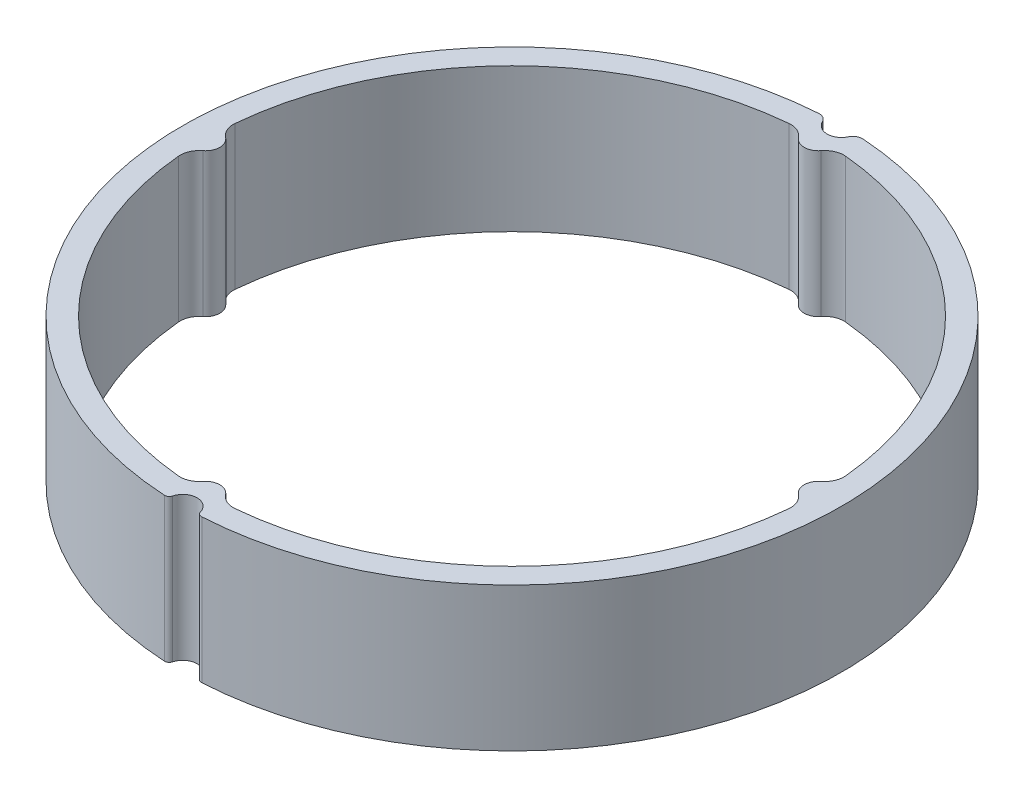
SolidWorks part; units mm, degrees
ref_plane "Front Plane" through (0, 0, 0) normal (0, 0, 1) x (1, 0, 0)
ref_plane "Top Plane" through (0, 0, 0) normal (0, 1, 0) x (1, 0, 0)
ref_plane "Right Plane" through (0, 0, 0) normal (1, 0, 0) x (0, 0, -1)
sketch "Sketch1" plane through (0, 0, 0) normal (0, 1, 0) x (1, 0, 0)
  line L3 (0, 0.002) -> (0, 3.7877) construction
  line L4 (0, 3.7877) -> (2.417, 3.7877)
  line L5 (0, 3.7877) -> (-2.417, 3.7877)
  arc A0 (1.9585, -34.3422) -> (34.0991, 4.542) centre (0, 0.002) ccw
  arc A2 (-2.417, 3.7877) -> (2.417, 3.7877) centre (0, 0.002) ccw
  circle A3 centre (0, 0.002) radius 34.4 construction
  arc A7 (-1.354, 33.756) -> (1.354, 33.756) centre (0, 34.4014) ccw
  arc A8 (34.0991, 4.542) -> (2.3243, 34.3234) centre (0, 0.002) ccw
  arc A9 (-2.3243, 34.3234) -> (-34.0991, 4.542) centre (0, 0.002) ccw
  arc A10 (-34.0991, 4.542) -> (-1.9585, -34.3422) centre (0, 0.002) ccw
  arc A11 (1.354, 33.756) -> (2.3243, 34.3234) centre (2.2567, 33.3257) cw
  arc A12 (-1.354, 33.756) -> (-2.3243, 34.3234) centre (-2.2567, 33.3257) ccw
  arc A13 (1.4475, -33.9741) -> (-1.4475, -33.9741) centre (0, -34.3673) ccw
  arc A14 (1.4475, -33.9741) -> (1.9585, -34.3422) centre (1.9301, -33.843) ccw
  arc A15 (-1.4475, -33.9741) -> (-1.9585, -34.3422) centre (-1.9301, -33.843) cw
  point P15 (1.4997, 34.3693)
  dimension "D2" = 4.834
  dimension "D3" = 4.4915
  dimension "D4" = 34.4
  dimension "D5" = 1
  dimension "D6" = 1.5
  dimension "D7" = 0.5
  dimension "D11" = 1.4997
sketch "Sketch2" plane through (0, 0, 0) normal (0, 1, 0) x (1, 0, 0)
  arc A0 (-31.8625, -2.9633) -> (-2.9633, -31.8625) centre (0, 0) ccw
  arc A1 (-1.1906, 31.0876) -> (1.1906, 31.0876) centre (0, 32) ccw
  arc A2 (31.0876, 1.1906) -> (31.0876, -1.1906) centre (32, 0) ccw
  arc A3 (1.1906, -31.0876) -> (-1.1906, -31.0876) centre (0, -32) ccw
  arc A4 (-31.0876, -1.1906) -> (-31.0876, 1.1906) centre (-32, 0) ccw
  arc A5 (-2.9633, 31.8625) -> (-31.8625, 2.9633) centre (0, 0) ccw
  arc A6 (31.8625, 2.9633) -> (2.9633, 31.8625) centre (0, 0) ccw
  arc A7 (2.9633, -31.8625) -> (31.8625, -2.9633) centre (0, 0) ccw
  arc A8 (-31.0876, -1.1906) -> (-31.8625, -2.9633) centre (-29.8711, -2.7781) ccw
  arc A9 (-31.0876, 1.1906) -> (-31.8625, 2.9633) centre (-29.8711, 2.7781) cw
  arc A10 (1.1906, -31.0876) -> (2.9633, -31.8625) centre (2.7781, -29.8711) ccw
  arc A11 (-1.1906, -31.0876) -> (-2.9633, -31.8625) centre (-2.7781, -29.8711) cw
  arc A12 (31.0876, 1.1906) -> (31.8625, 2.9633) centre (29.8711, 2.7781) ccw
  arc A13 (31.0876, -1.1906) -> (31.8625, -2.9633) centre (29.8711, -2.7781) cw
  arc A14 (1.1906, 31.0876) -> (2.9633, 31.8625) centre (2.7781, 29.8711) cw
  arc A15 (-1.1906, 31.0876) -> (-2.9633, 31.8625) centre (-2.7781, 29.8711) ccw
  point P21 (1.4996, -31.9648)
  point P26 (31.9648, 1.4996)
  point P33 (-1.4996, 31.9648)
  dimension "D1" = 32
  dimension "D2" = 1.5
  dimension "D3" = 1.5
  dimension "D4" = 1.5
  dimension "D5" = 1.5
  dimension "D6" = 2
extrude "Boss-Extrude1" add sketch "Sketch1" along normal blind 15 contours A10 A0 A8 A7 A9 A2 L5 L4 region at (2.206, 0, 33.46)
extrude "Cut-Extrude2" cut sketch "Sketch2" along normal through all
